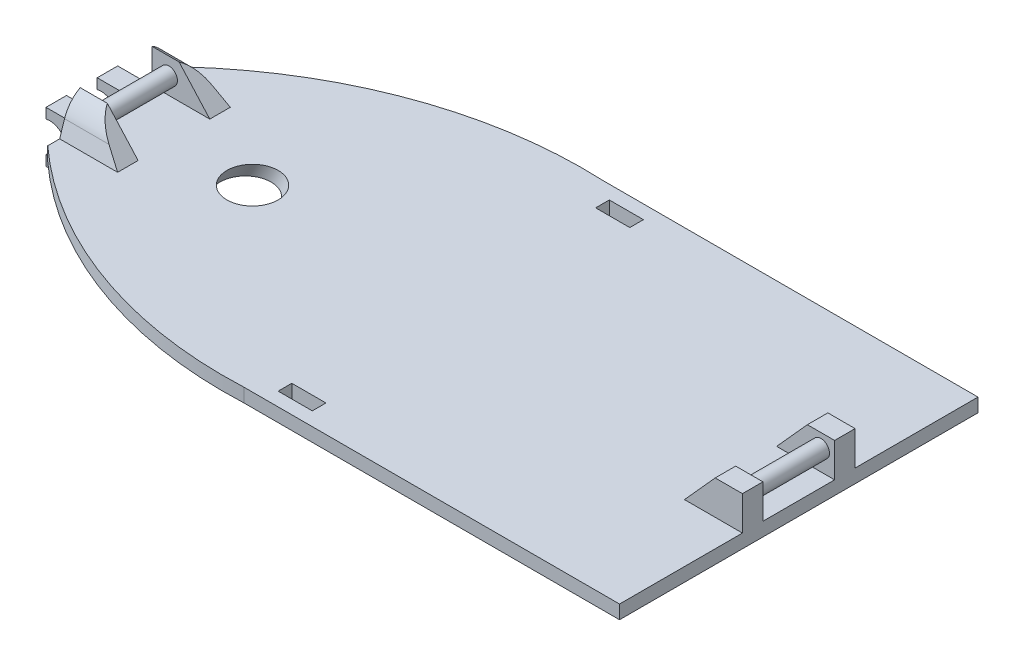
SolidWorks part; units mm, degrees
ref_plane "Front Plane" through (0, 0, 0) normal (0, 0, 1) x (1, 0, 0)
ref_plane "Top Plane" through (0, 0, 0) normal (0, 1, 0) x (1, 0, 0)
ref_plane "Right Plane" through (0, 0, 0) normal (1, 0, 0) x (0, 0, -1)
sketch "Sketch1" plane through (0, 0, 0) normal (0, 1, 0) x (1, 0, 0)
  line L0 (-110, 0) -> (0, 0)
  line L1 (0, 0) -> (0, -105)
  line L2 (0, -105) -> (-110, -105)
  line L4 (-200, -72.5) -> (-200, -32.5)
  arc A2 (-200, -32.5) -> (-110, 0) centre (-115.7774, -124.8664) cw
  arc A3 (-200, -72.5) -> (-110, -105) centre (-115.7774, 19.8664) ccw
  point P11 (-200, -52.5)
  point P12 (0, -52.5)
  dimension "D4" = 40
  dimension "D6" = 125
  dimension "D7" = 125
  dimension "D1" = 110
  dimension "D2" = 105
  dimension "D3" = 200
  dimension "D5" = 110
extrude "Boss-Extrude1" add sketch "Sketch1" along normal blind 4
sketch "Sketch2" plane through (0, 0, 105) normal (0, 0, 1) x (1, 0, 0)
  line L0 (-200, 4) -> (-210, 4)
  line L1 (-188, 0) -> (-200, -11)
  line L2 (57.8969, 0) -> (-57.8969, 0) construction
  line L3 (-200, -11) -> (-210, -11)
  line L4 (-210, 4) -> (-210, 1)
  line L5 (-210, -11) -> (-210, -8)
  line L6 (-200, 4) -> (-188, 0)
  arc A0 (-210, 1) -> (-210, -8) centre (-208.8457, -3.5) cw
  point P11 (-204.2, -3.5)
  dimension "D8" = 4.6457
  dimension "D1" = 10
  dimension "D2" = 15
  dimension "D3" = 3
  dimension "D4" = 3
  dimension "D5" = 10
  dimension "D6" = 5.8
  dimension "D7" = 22
extrude "Boss-Extrude2" add sketch "Sketch2" along normal mid plane 6 from offset 45 offset against normal yes
ref_plane "Plane1" through (0, 0, 52.5) normal (0, 0, 1) x (1, 0, 0)
mirror "Mirror1" about plane through (0, 0, 52.5) normal (0, 0, 1) of "Boss-Extrude2"
ref_plane "Plane2" through (-100, 0, 0) normal (1, 0, 0) x (0, 0, -1)
sketch "Sketch5" plane through (0, 0, 105) normal (0, 0, 1) x (1, 0, 0)
  line L0 (-16.9798, 4) -> (-7.9798, 14)
  line L1 (-110, 4) -> (0, 4) construction
  line L2 (-7.9798, 14) -> (0, 14)
  line L3 (0, 14) -> (0, 4)
  line L4 (0, 4) -> (-16.9798, 4)
  dimension "D1" = 10
  dimension "D2" = 9
extrude "Boss-Extrude3" add sketch "Sketch5" along direction (0, 0, 1) on the side of the normal mid plane 6 from offset 39 contours L2 L3 L4 L0 offset against normal yes
mirror "Mirror4" about plane through (0, 0, 52.5) normal (0, 0, 1) of "Boss-Extrude3"
sketch "Sketch6" plane through (0, 0, 42) normal (0, 0, 1) x (1, 0, 0)
  line L0 (0, -13.75) -> (0, 13.75) construction
  line L1 (-110, 4) -> (0, 4) construction
  circle A0 centre (-4, 10) radius 2.5
  dimension "D1" = 5
  dimension "D2" = 4
  dimension "D3" = 6
extrude "Boss-Extrude4" add sketch "Sketch6" along normal up to body separate body
sketch "Sketch7" plane through (0, 4, 0) normal (0, 1, 0) x (1, 0, 0)
  line L0 (-110, -105) -> (0, -105) construction
  line L1 (-104, -101) -> (-94, -101)
  line L2 (-104, -101) -> (-104, -97)
  line L3 (-104, -97) -> (-94, -97)
  line L4 (-94, -101) -> (-94, -97)
  dimension "D1" = 6
  dimension "D2" = 10
  dimension "D3" = 4
  dimension "D4" = 4
extrude "Cut-Extrude1" cut sketch "Sketch7" against normal blind 10
mirror "Mirror5" about plane through (0, 0, 52.5) normal (0, 0, 1) of "Cut-Extrude1"
sketch "Sketch8" plane through (0, 4, 0) normal (0, 1, 0) x (1, 0, 0)
  line L0 (-13.75, -52.5) -> (13.75, -52.5) construction
  line L1 (-200, -48) -> (-200, -57) construction
  circle A0 centre (-160, -52.5) radius 7.5
  dimension "D2" = 15
  dimension "D1" = 40
sketch "Sketch9" plane through (0, 0, 52.5) normal (0, 0, 1) x (1, 0, 0)
  line L0 (-160, 4) -> (-163.8674, -3.4662)
  line L1 (-152.5, 4) -> (-167.5, 4) construction
sweep "Cut-Sweep1" cut profiles "Sketch8" path "Sketch9"
mirror "Mirror6" about plane through (-100, 0, 0) normal (1, 0, 0) of "Boss-Extrude3", "Mirror4"
chamfer "Chamfer1" distance 10 angle 18 2 edges at (-196.0101, 14, 69) (-196.0101, 14, 36) first distance on face at (-193.7601, 9, 69) first distance on face at (-193.7601, 9, 36)
fillet "Fillet1" radius 10 2 edges at (-196.0101, 14, 39.2492) (-196.0101, 14, 65.7508)
sketch "Sketch10" plane through (0, 0, 42) normal (0, 0, 1) x (1, 0, 0)
  line L0 (-200, 14) -> (-200, 8.3947) construction
  line L1 (-192.0202, 14) -> (-200, 14) construction
  circle A0 centre (-195, 9) radius 2.5
  dimension "D1" = 5
  dimension "D2" = 5
  dimension "D3" = 5
extrude "Boss-Extrude6" add sketch "Sketch10" along normal blind 23 contours A0
